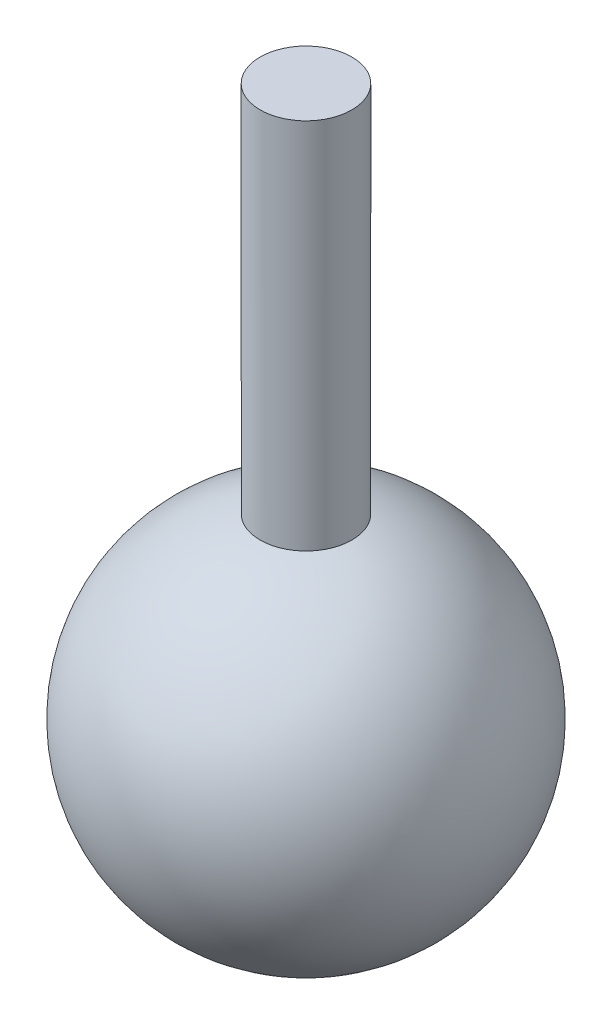
SolidWorks part; units mm, degrees
material "ABS"
ref_plane "Front Plane" through (0, 0, 0) normal (0, 0, 1) x (1, 0, 0)
ref_plane "Top Plane" through (0, 0, 0) normal (0, 1, 0) x (1, 0, 0)
ref_plane "Right Plane" through (0, 0, 0) normal (1, 0, 0) x (0, 0, -1)
sketch "Sketch1" plane through (0, 0, 0) normal (0, 0, 1) x (1, 0, 0)
  line L0 (0, 12.7) -> (0, -12.7)
  line L1 (0, 12.7) -> (0, 38.1)
  line L2 (0, 38.1) -> (-3.175, 38.1)
  line L3 (-3.175, 38.1) -> (-3.175, 12.2967)
  arc A0 (0, -12.7) -> (0, 12.7) centre (0, 0) cw
  dimension "D1" = 25.4
  dimension "D2" = 25.4
  dimension "D3" = 3.175
revolve "Revolve1" add sketch "Sketch1" angle 360 about L1 region at (-1.5917, 25.3329, 0) region at (-5.39, 0, 0)
